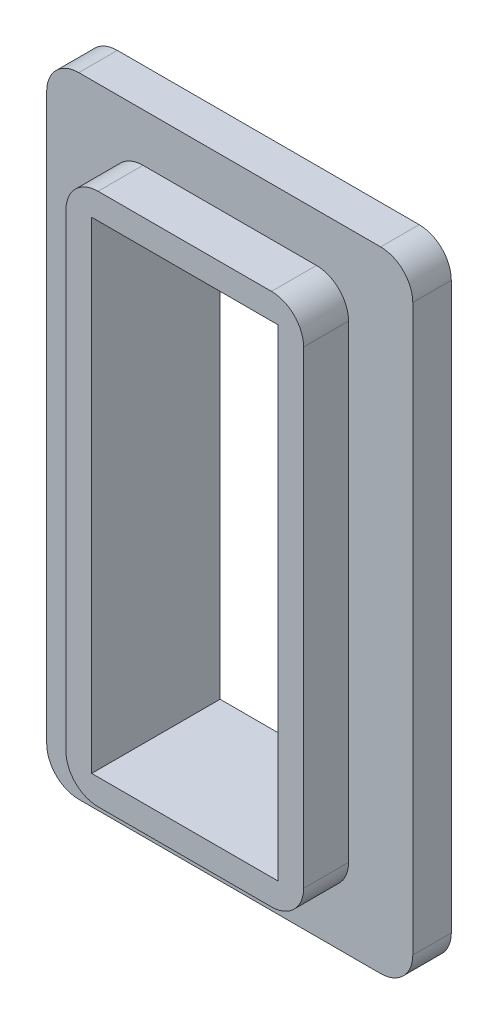
SolidWorks part; units mm, degrees
ref_plane "Top Plane" through (0, 0, 0) normal (0, 0, 1) x (1, 0, 0)
ref_plane "Front Plane" through (0, 0, 0) normal (0, 1, 0) x (1, 0, 0)
ref_plane "Right Plane" through (0, 0, 0) normal (1, 0, 0) x (0, 0, -1)
sketch "Sketch1" plane through (0, 0, 0) normal (0, 0, 1) x (1, 0, 0)
  line L6 (5.7, -9.8) -> (-5.7, -9.8)
  line L9 (-2.9, -7.5) -> (2.9, -7.5)
  line L10 (-2.9, -7.5) -> (-2.9, 7.5)
  line L11 (-2.9, 7.5) -> (2.9, 7.5)
  line L12 (2.9, -7.5) -> (2.9, 7.5)
  line L13 (-2.9, -7.5) -> (2.9, 7.5) construction
  line L14 (-2.9, 7.5) -> (2.9, -7.5) construction
  line L15 (-3.7, -8.3) -> (3.7, -8.3)
  line L16 (-3.7, -8.3) -> (-3.7, 8.3)
  line L17 (-3.7, 8.3) -> (3.7, 8.3)
  line L18 (3.7, -8.3) -> (3.7, 8.3)
  line L19 (-3.7, -8.3) -> (3.7, 8.3) construction
  line L20 (-3.7, 8.3) -> (3.7, -8.3) construction
  line L21 (5.7, -9.8) -> (5.7, 9.8)
  line L22 (5.7, 9.8) -> (-5.7, 9.8)
  line L23 (-5.7, -9.8) -> (-5.7, 9.8)
  line L24 (5.7, -9.8) -> (-5.7, 9.8) construction
  line L25 (5.7, 9.8) -> (-5.7, -9.8) construction
  point P0 (0, 0)
  point P15 (0, 0)
  point P20 (0, 0)
  dimension "D1" = 0.8
  dimension "D2" = 1.5
  dimension "D4" = 5.8
  dimension "D3" = 0.8
  dimension "D5" = 15
  dimension "D6" = 2
  dimension "D7" = 11.4
  dimension "D8" = 19.6
  dimension "D9" = 16.6
  dimension "D10" = 7.4
extrude "Boss-Extrude1" add sketch "Sketch1" along normal blind 0.6 and the other way blind 0.6 contours L23 L6 L21 L22 L18 L15 L16 L17 | L15 L18 L17 L16 L12 L9 L10 L11 | L9 L12 L11 L10 region at (0, -9.5733, 0) region at (0, 0, 0) region at (-3.5183, 0, 0)
extrude "Boss-Extrude2" add sketch "Sketch1<3>" along normal blind 2 and the other way blind 2 contours L11 L12 L9 L10 | L17 L18 L15 L16
sketch "Sketch1<3>" plane through (0, 0, 0) normal (0, 0, 1) x (1, 0, 0) same geometry as "Sketch1"
extrude "Cut-Extrude1" cut sketch "Sketch1<4>" against normal through all both and the other way through all contours L11 L12 L9 L10
sketch "Sketch1<4>" plane through (0, 0, 0) normal (0, 0, 1) x (1, 0, 0) same geometry as "Sketch1"
fillet "Fillet1" radius 1 12 edges at (-3.7, 8.3, -1.3) (3.7, 8.3, -1.3) (3.7, -8.3, -1.3) (-3.7, -8.3, -1.3) (-5.7, -9.8, 0) (5.7, -9.8, 0) (3.7, -8.3, 1.3) (-3.7, -8.3, 1.3) (-3.7, 8.3, 1.3) (3.7, 8.3, 1.3) (5.7, 9.8, 0) (-5.7, 9.8, 0)
